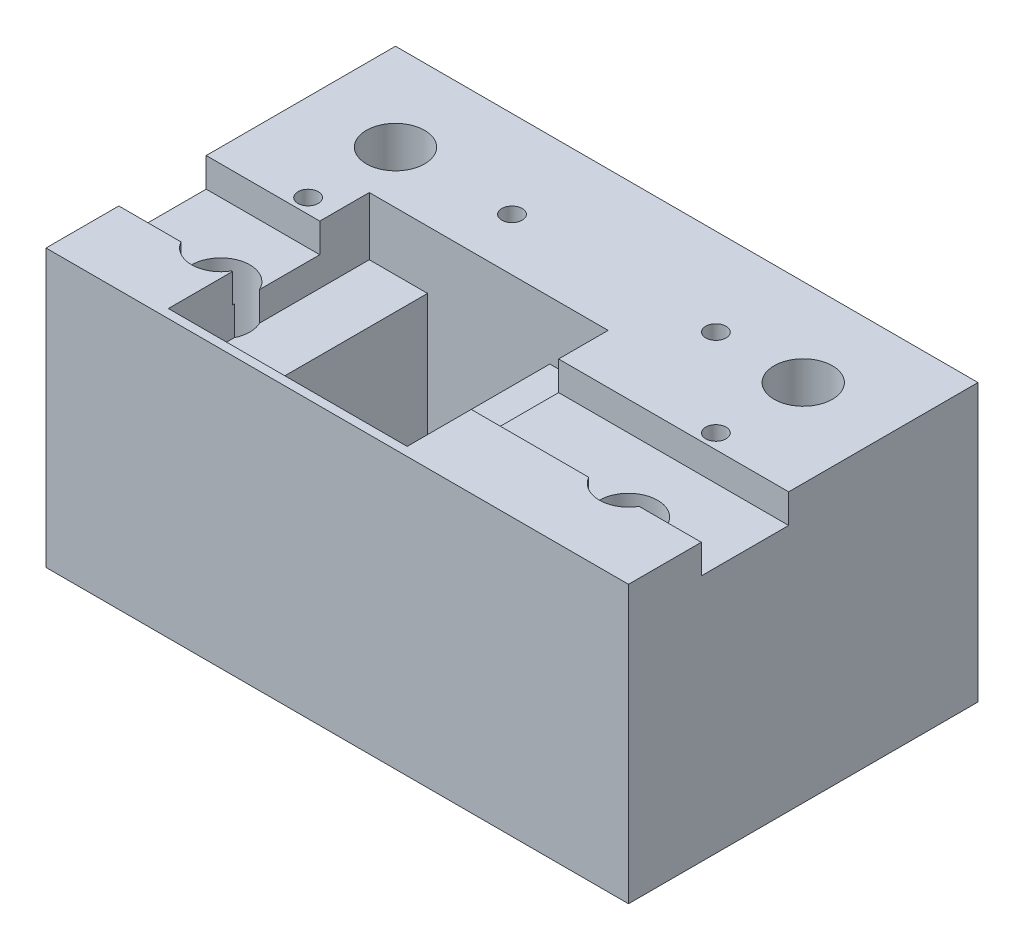
SolidWorks part; units mm, degrees
ref_plane "前视基准面" through (0, 0, 0) normal (0, 0, 1) x (1, 0, 0)
ref_plane "上视基准面" through (0, 0, 0) normal (0, 1, 0) x (1, 0, 0)
ref_plane "右视基准面" through (0, 0, 0) normal (1, 0, 0) x (0, 0, -1)
other "Configuration Table"
sketch "草图1" plane through (0, 0, 0) normal (0, 1, 0) x (1, 0, 0)
  line L1 (0, 0) -> (20, 0)
  line L2 (0, 0) -> (0, -12)
  line L3 (0, -12) -> (20, -12)
  line L4 (20, 0) -> (20, -12)
  line L9 (3.9, -4.8) -> (12.1, -4.8)
  line L10 (0, -6.5) -> (20, -6.5)
  line L11 (0, -6.5) -> (0, -9.5)
  line L12 (0, -9.5) -> (20, -9.5)
  line L13 (20, -6.5) -> (20, -9.5)
  line L14 (3.9, -4.8) -> (3.9, -11.7)
  line L15 (3.9, -11.7) -> (12.1, -11.7)
  line L16 (12.1, -4.8) -> (12.1, -11.7)
  line L17 (5.9, -4.8) -> (10.1, -4.8)
  line L18 (5.9, -4.8) -> (5.9, -11.7)
  line L19 (5.9, -11.7) -> (10.1, -11.7)
  line L20 (10.1, -4.8) -> (10.1, -11.7)
  dimension "D1" = 12
  dimension "D2" = 20
  dimension "D3" = 0.3
  dimension "D4" = 6.9
  dimension "D5" = 5.9
  dimension "D6" = 3
  dimension "D7" = 9.9
  dimension "D8" = 2.5
  dimension "D9" = 2
  dimension "D10" = 2
extrude "凸台-拉伸1" add sketch "草图1" along normal blind 9.5 contours L4 L3 L2 L1 | L18 L19 L20 L17
extrude "切除-拉伸2" cut sketch "草图1<4>" against normal blind 1 from surface contours L10 L13 L12 L11 starting at face at (8, 9.5, 8.25)
sketch "草图1<4>" plane through (0, 0, 0) normal (0, 1, 0) x (1, 0, 0) same geometry as "草图1"
extrude "切除-拉伸4" cut sketch "草图1<6>" against normal blind 2 from surface contours L9 L16 L15 L14 starting at face at (9, 9.5, 4.45)
sketch "草图1<6>" plane through (0, 0, 0) normal (0, 1, 0) x (1, 0, 0) same geometry as "草图1"
sketch "草图2" plane through (0, 9.5, 0) normal (0, 1, 0) x (1, 0, 0)
  line L0 (0, 0) -> (20, 0) construction
  line L1 (0, 0) -> (0, -6.5) construction
  line L2 (0, -12) -> (20, -12) construction
  line L3 (20, 0) -> (20, -6.5) construction
  line L4 (0, -6.5) -> (0, -9.5) construction
  circle A0 centre (3, -3) radius 1
  circle A1 centre (3, -3) radius 0.7
  circle A2 centre (3, -9) radius 1
  circle A3 centre (3, -9) radius 0.7
  circle A4 centre (17, -3) radius 0.7
  circle A5 centre (17, -3) radius 1
  circle A6 centre (17, -9) radius 0.7
  circle A7 centre (17, -9) radius 1
  circle A8 centre (7, -3) radius 0.35
  circle A9 centre (14, -3) radius 0.35
  circle A10 centre (3, -6) radius 0.35
  circle A11 centre (17, -6) radius 0.35
  point P30 (0, 0)
  point P33 (4.1934, -5.1085)
  point P36 (4.6512, -3.7593)
  dimension "D1" = 1.4
  dimension "D2" = 2
  dimension "D11" = 0.7
  dimension "D3" = 3
  dimension "D4" = 3
  dimension "D5" = 3
  dimension "D6" = 3
  dimension "D7" = 3
  dimension "D8" = 3
  dimension "D9" = 3
  dimension "D10" = 3
  dimension "D12" = 3
  dimension "D13" = 7
  dimension "D14" = 3
  dimension "D15" = 6
  dimension "D16" = 6
  dimension "D17" = 3
  dimension "D18" = 3
  dimension "D19" = 6
extrude "切除-拉伸5" cut sketch "草图2" against normal through all contours A1 | A3 | A4 | A6 | A10 | A8 | A9 | A11
extrude "切除-拉伸6" cut sketch "草图2<3>" against normal offset from surface (7.5 mm away) 2 contours A0 | A5 | A7 | A2 up to face at (3, 0, 6.35)
sketch "草图2<3>" plane through (0, 9.5, 0) normal (0, 1, 0) x (1, 0, 0) same geometry as "草图2"
